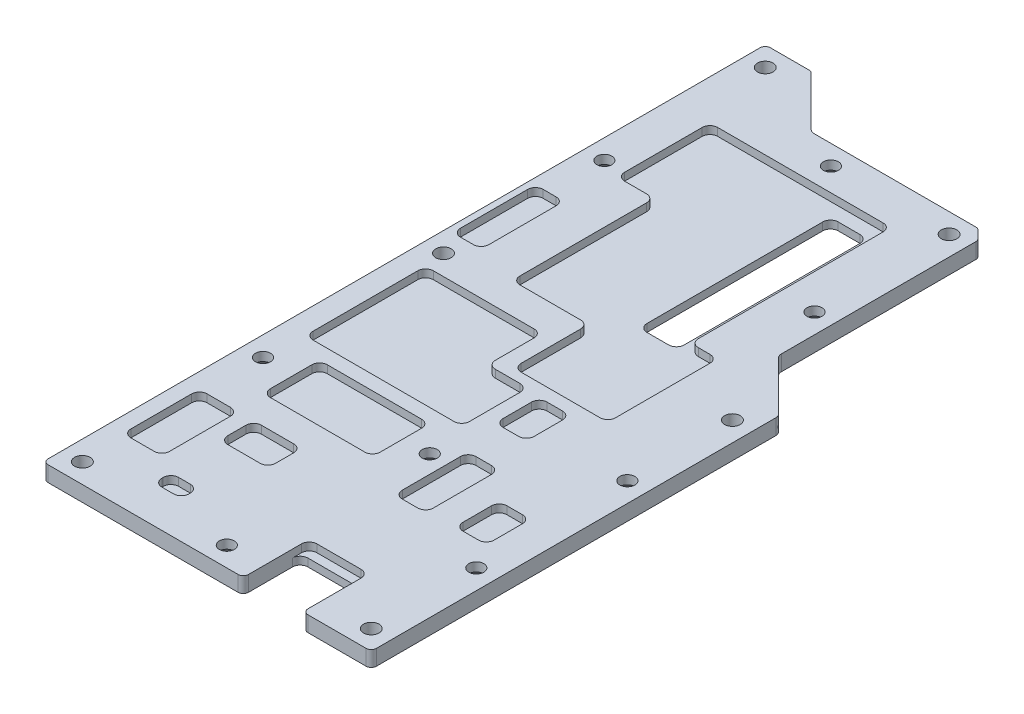
SolidWorks part; units mm, degrees
ref_plane "Front Plane" through (0, 0, 0) normal (0, 0, 1) x (1, 0, 0)
ref_plane "Top Plane" through (0, 0, 0) normal (0, 1, 0) x (1, 0, 0)
ref_plane "Right Plane" through (0, 0, 0) normal (1, 0, 0) x (0, 0, -1)
sketch "Sketch1" plane through (0, 0, 0) normal (0, 1, 0) x (1, 0, 0)
  line L0 (0, 1) -> (0, 138.7)
  line L1 (1, 0) -> (37.75, 0)
  line L2 (63.5, 1) -> (63.5, 78.3258)
  line L3 (1, 139.7) -> (8.4758, 139.7)
  line L4 (19.6713, 129.54) -> (50.8958, 129.54)
  line L5 (9.1829, 139.4071) -> (18.6107, 129.9793)
  line L6 (53.34, 89.5213) -> (53.34, 127.0958)
  line L7 (63.2071, 79.0329) -> (53.7793, 88.4607)
  line L8 (51.6029, 129.2471) -> (53.0471, 127.8029)
  line L13 (38.75, 1) -> (38.75, 9.5)
  line L14 (40.25, 11) -> (48.75, 11)
  line L15 (50.25, 9.5) -> (50.25, 1)
  line L16 (51.25, 0) -> (62.5, 0)
  arc A2 (1, 0) -> (0, 1) centre (1, 1) cw
  arc A3 (63.5, 1) -> (62.5, 0) centre (62.5, 1) cw
  arc A4 (53.7793, 88.4607) -> (53.34, 89.5213) centre (54.84, 89.5213) cw
  arc A5 (18.6107, 129.9793) -> (19.6713, 129.54) centre (19.6713, 131.04) ccw
  arc A6 (63.5, 78.3258) -> (63.2071, 79.0329) centre (62.5, 78.3258) ccw
  arc A7 (53.34, 127.0958) -> (53.0471, 127.8029) centre (52.34, 127.0958) ccw
  arc A8 (51.6029, 129.2471) -> (50.8958, 129.54) centre (50.8958, 128.54) ccw
  arc A9 (9.1829, 139.4071) -> (8.4758, 139.7) centre (8.4758, 138.7) ccw
  arc A10 (1, 139.7) -> (0, 138.7) centre (1, 138.7) ccw
  arc A13 (48.75, 11) -> (50.25, 9.5) centre (48.75, 9.5) cw
  arc A14 (38.75, 9.5) -> (40.25, 11) centre (40.25, 9.5) cw
  arc A15 (50.25, 1) -> (51.25, 0) centre (51.25, 1) ccw
  arc A16 (38.75, 1) -> (37.75, 0) centre (37.75, 1) cw
  point P20 (0, 0)
  point P23 (63.5, 0)
  point P26 (53.34, 88.9)
  point P29 (19.05, 129.54)
  point P32 (63.5, 78.74)
  point P35 (53.34, 127.51)
  point P38 (51.31, 129.54)
  point P41 (8.89, 139.7)
  point P44 (0, 139.7)
  point P45 (38.75, 11)
  point P48 (50.25, 0)
  point P51 (38.75, 0)
  dimension "D14" = 1.5
  dimension "D15" = 1
  dimension "D16" = 1
  dimension "D17" = 1.5
  dimension "D18" = 1
  dimension "D19" = 1
  dimension "D1" = 139.7
  dimension "D2" = 63.5
  dimension "D3" = 78.74
  dimension "D4" = 8.89
  dimension "D5" = 10.16
  dimension "D6" = 10.16
  dimension "D7" = 32.26
  dimension "D8" = 10.16
  dimension "D9" = 10.16
  dimension "D10" = 2.03
  dimension "D11" = 13.25
  dimension "D12" = 11.5
  dimension "D13" = 11
extrude "Boss-Extrude1" add sketch "Sketch1" along normal blind 3
sketch "Sketch2" plane through (0, 3, 0) normal (0, 1, 0) x (1, 0, 0)
  line L36 (50.25, 0) -> (50.25, 11.25)
  line L37 (51.25, 0) -> (62.5, 0) construction
  line L38 (48.75, 12.75) -> (40.25, 12.75)
  line L39 (38.75, 11.25) -> (38.75, 0)
  line L40 (1, 0) -> (37.75, 0) construction
  line L41 (38.75, 0) -> (50.25, 0)
  line L42 (63.5, 1) -> (63.5, 78.3258) construction
  line L43 (0, 138.7) -> (0, 1) construction
  line L44 (52.25, 37.5) -> (55.25, 37.5)
  line L45 (50.75, 36) -> (50.75, 30.5)
  line L46 (52.25, 29) -> (55.25, 29)
  line L47 (56.75, 36) -> (56.75, 30.5)
  line L48 (41, 42.75) -> (44, 42.75)
  line L49 (39.5, 41.25) -> (39.5, 30)
  line L50 (41, 28.5) -> (44, 28.5)
  line L51 (45.5, 41.25) -> (45.5, 30)
  line L52 (11.25, 43.75) -> (29.5, 43.75)
  line L53 (9.75, 42.25) -> (9.75, 34.25)
  line L54 (11.25, 32.75) -> (29.5, 32.75)
  line L55 (31, 42.25) -> (31, 34.25)
  line L56 (18, 10.5) -> (15.75, 10.5)
  line L57 (19.5, 9) -> (19.5, 8.75)
  line L58 (18, 7.25) -> (15.75, 7.25)
  line L59 (14.25, 9) -> (14.25, 8.75)
  line L60 (4.25, 68.25) -> (4.25, 48)
  line L61 (4.5, 27.25) -> (9, 27.25)
  line L62 (3, 25.75) -> (3, 14)
  line L63 (4.5, 12.5) -> (9, 12.5)
  line L64 (10.5, 25.75) -> (10.5, 14)
  line L65 (15, 27.25) -> (21.25, 27.25)
  line L66 (13.5, 25.75) -> (13.5, 22.25)
  line L67 (15, 20.75) -> (21.25, 20.75)
  line L68 (22.75, 25.75) -> (22.75, 22.25)
  line L69 (5.75, 46.5) -> (33, 46.5)
  line L70 (34.5, 48) -> (34.5, 57.75)
  line L71 (33, 59.25) -> (28.25, 59.25)
  line L72 (26.75, 60.75) -> (26.75, 68.25)
  line L73 (25.25, 69.75) -> (5.75, 69.75)
  line L74 (31.25, 61.25) -> (46.5, 61.25)
  line L75 (38.75, 58.75) -> (41.75, 58.75)
  line L76 (37.25, 57.25) -> (37.25, 51.75)
  line L77 (38.75, 50.25) -> (41.75, 50.25)
  line L78 (43.25, 57.25) -> (43.25, 51.75)
  line L79 (48, 62.75) -> (48, 81)
  line L80 (46.5, 82.5) -> (44.25, 82.5)
  line L81 (42.75, 84) -> (42.75, 119.75)
  line L82 (41.25, 121.25) -> (9.25, 121.25)
  line L83 (7.75, 119.75) -> (7.75, 104.75)
  line L84 (9.25, 103.25) -> (13.5, 103.25)
  line L85 (15, 101.75) -> (15, 77.25)
  line L86 (16.5, 75.75) -> (28.25, 75.75)
  line L87 (29.75, 74.25) -> (29.75, 62.75)
  line L89 (2.75, 94) -> (5.25, 94)
  line L90 (1.25, 92.5) -> (1.25, 79.5)
  line L91 (2.75, 78) -> (5.25, 78)
  line L92 (6.75, 92.5) -> (6.75, 79.5)
  arc A32 (50.25, 11.25) -> (48.75, 12.75) centre (48.75, 11.25) ccw
  arc A33 (40.25, 12.75) -> (38.75, 11.25) centre (40.25, 11.25) ccw
  arc A34 (50.75, 30.5) -> (52.25, 29) centre (52.25, 30.5) ccw
  arc A35 (55.25, 29) -> (56.75, 30.5) centre (55.25, 30.5) ccw
  arc A36 (56.75, 36) -> (55.25, 37.5) centre (55.25, 36) ccw
  arc A37 (50.75, 36) -> (52.25, 37.5) centre (52.25, 36) cw
  arc A38 (39.5, 30) -> (41, 28.5) centre (41, 30) ccw
  arc A39 (44, 28.5) -> (45.5, 30) centre (44, 30) ccw
  arc A40 (44, 42.75) -> (45.5, 41.25) centre (44, 41.25) cw
  arc A41 (41, 42.75) -> (39.5, 41.25) centre (41, 41.25) ccw
  arc A42 (29.5, 43.75) -> (31, 42.25) centre (29.5, 42.25) cw
  arc A43 (29.5, 32.75) -> (31, 34.25) centre (29.5, 34.25) ccw
  arc A44 (9.75, 34.25) -> (11.25, 32.75) centre (11.25, 34.25) ccw
  arc A45 (11.25, 43.75) -> (9.75, 42.25) centre (11.25, 42.25) ccw
  arc A46 (19.5, 8.75) -> (18, 7.25) centre (18, 8.75) cw
  arc A47 (18, 10.5) -> (19.5, 9) centre (18, 9) cw
  arc A48 (15.75, 7.25) -> (14.25, 8.75) centre (15.75, 8.75) cw
  arc A49 (15.75, 10.5) -> (14.25, 9) centre (15.75, 9) ccw
  arc A50 (21.25, 20.75) -> (22.75, 22.25) centre (21.25, 22.25) ccw
  arc A51 (21.25, 27.25) -> (22.75, 25.75) centre (21.25, 25.75) cw
  arc A52 (15, 27.25) -> (13.5, 25.75) centre (15, 25.75) ccw
  arc A53 (13.5, 22.25) -> (15, 20.75) centre (15, 22.25) ccw
  arc A54 (3, 14) -> (4.5, 12.5) centre (4.5, 14) ccw
  arc A55 (9, 12.5) -> (10.5, 14) centre (9, 14) ccw
  arc A56 (9, 27.25) -> (10.5, 25.75) centre (9, 25.75) cw
  arc A57 (4.5, 27.25) -> (3, 25.75) centre (4.5, 25.75) ccw
  arc A58 (26.75, 68.25) -> (25.25, 69.75) centre (25.25, 68.25) ccw
  arc A59 (34.5, 57.75) -> (33, 59.25) centre (33, 57.75) ccw
  arc A60 (33, 46.5) -> (34.5, 48) centre (33, 48) ccw
  arc A61 (4.25, 48) -> (5.75, 46.5) centre (5.75, 48) ccw
  arc A62 (5.75, 69.75) -> (4.25, 68.25) centre (5.75, 68.25) ccw
  arc A63 (28.25, 59.25) -> (26.75, 60.75) centre (28.25, 60.75) cw
  arc A64 (41.75, 58.75) -> (43.25, 57.25) centre (41.75, 57.25) cw
  arc A65 (41.75, 50.25) -> (43.25, 51.75) centre (41.75, 51.75) ccw
  arc A66 (37.25, 51.75) -> (38.75, 50.25) centre (38.75, 51.75) ccw
  arc A67 (38.75, 58.75) -> (37.25, 57.25) centre (38.75, 57.25) ccw
  arc A68 (42.75, 119.75) -> (41.25, 121.25) centre (41.25, 119.75) ccw
  arc A69 (44.25, 82.5) -> (42.75, 84) centre (44.25, 84) cw
  arc A70 (48, 81) -> (46.5, 82.5) centre (46.5, 81) ccw
  arc A71 (46.5, 61.25) -> (48, 62.75) centre (46.5, 62.75) ccw
  arc A72 (31.25, 61.25) -> (29.75, 62.75) centre (31.25, 62.75) cw
  arc A73 (28.25, 75.75) -> (29.75, 74.25) centre (28.25, 74.25) cw
  arc A74 (15, 77.25) -> (16.5, 75.75) centre (16.5, 77.25) ccw
  arc A75 (13.5, 103.25) -> (15, 101.75) centre (13.5, 101.75) cw
  arc A76 (7.75, 104.75) -> (9.25, 103.25) centre (9.25, 104.75) ccw
  arc A77 (9.25, 121.25) -> (7.75, 119.75) centre (9.25, 119.75) ccw
  arc A78 (1.25, 79.5) -> (2.75, 78) centre (2.75, 79.5) ccw
  arc A79 (5.25, 78) -> (6.75, 79.5) centre (5.25, 79.5) ccw
  arc A80 (5.25, 94) -> (6.75, 92.5) centre (5.25, 92.5) cw
  arc A81 (2.75, 94) -> (1.25, 92.5) centre (2.75, 92.5) ccw
  point P12 (50.25, 12.75)
  point P15 (38.75, 12.75)
  point P22 (50.75, 29)
  point P25 (56.75, 29)
  point P28 (56.75, 37.5)
  point P37 (39.5, 28.5)
  point P40 (45.5, 28.5)
  point P43 (45.5, 42.75)
  point P56 (31, 32.75)
  point P59 (9.75, 32.75)
  point P62 (9.75, 43.75)
  point P69 (19.5, 7.25)
  point P72 (19.5, 10.5)
  point P77 (14.25, 10.5)
  point P90 (22.75, 27.25)
  point P93 (13.5, 27.25)
  point P96 (13.5, 20.75)
  point P99 (3, 12.5)
  point P104 (10.5, 27.25)
  point P107 (3, 27.25)
  point P117 (26.75, 69.75)
  point P120 (34.5, 59.25)
  point P123 (34.5, 46.5)
  point P126 (4.25, 46.5)
  point P129 (4.25, 69.75)
  point P137 (43.25, 58.75)
  point P142 (37.25, 50.25)
  point P145 (37.25, 58.75)
  point P158 (42.75, 121.25)
  point P161 (42.75, 82.5)
  point P164 (48, 82.5)
  point P167 (48, 61.25)
  point P170 (29.75, 61.25)
  point P175 (15, 75.75)
  point P178 (15, 103.25)
  point P181 (7.75, 103.25)
  point P184 (7.75, 121.25)
  point P192 (1.25, 78)
  point P197 (6.75, 94)
  point P200 (1.25, 94)
  dimension "D35" = 30.25
  dimension "D36" = 12.75
  dimension "D37" = 22.5
  dimension "D38" = 4.25
  dimension "D39" = 46.5
  dimension "D40" = 1.5
  dimension "D41" = 1.5
  dimension "D42" = 8.5
  dimension "D4" = 1.5
  dimension "D9" = 1.5
  dimension "D14" = 1.5
  dimension "D19" = 1.5
  dimension "D24" = 1.5
  dimension "D33" = 1.5
  dimension "D46" = 1.5
  dimension "D57" = 1.5
  dimension "D62" = 1.5
  dimension "D1" = 13.25
  dimension "D2" = 12.75
  dimension "D3" = 11.5
  dimension "D5" = 6
  dimension "D6" = 8.5
  dimension "D7" = 6.75
  dimension "D8" = 29
  dimension "D10" = 14.25
  dimension "D11" = 6
  dimension "D12" = 18
  dimension "D13" = 28.5
  dimension "D15" = 21.25
  dimension "D16" = 11
  dimension "D17" = 32.75
  dimension "D18" = 9.75
  dimension "D20" = 3.25
  dimension "D21" = 5.25
  dimension "D22" = 7.25
  dimension "D23" = 14.25
  dimension "D25" = 14.75
  dimension "D26" = 7.5
  dimension "D27" = 12.5
  dimension "D28" = 3
  dimension "D29" = 6.5
  dimension "D30" = 9.25
  dimension "D31" = 13.5
  dimension "D32" = 20.75
  dimension "D34" = 23.25
  dimension "D43" = 6
  dimension "D44" = 20.25
  dimension "D45" = 50.25
  dimension "D47" = 18.25
  dimension "D48" = 21.25
  dimension "D49" = 5.25
  dimension "D50" = 38.75
  dimension "D51" = 35
  dimension "D52" = 18
  dimension "D53" = 7.25
  dimension "D54" = 27.5
  dimension "D55" = 15.5
  dimension "D56" = 61.25
  dimension "D58" = 16
  dimension "D59" = 5.5
  dimension "D60" = 1.25
  dimension "D61" = 78
extrude "Cut-Extrude1" cut sketch "Sketch2" against normal blind 1.5
sketch "Sketch3" plane through (0, 0, 0) normal (0, -1, 0) x (-1, 0, 0)
  line L0 (-37.34, 118.58) -> (-37.34, 81.58) construction
  line L1 (-39.44, 118.58) -> (-35.24, 118.58)
  line L2 (-40.94, 117.08) -> (-40.94, 83.08)
  line L3 (-39.44, 81.58) -> (-35.24, 81.58)
  line L4 (-33.74, 117.08) -> (-33.74, 83.08)
  line L5 (-40.94, 100.08) -> (-33.74, 100.08) construction
  arc A0 (-40.94, 83.08) -> (-39.44, 81.58) centre (-39.44, 83.08) ccw
  arc A1 (-35.24, 81.58) -> (-33.74, 83.08) centre (-35.24, 83.08) ccw
  arc A2 (-35.24, 118.58) -> (-33.74, 117.08) centre (-35.24, 117.08) cw
  arc A3 (-39.44, 118.58) -> (-40.94, 117.08) centre (-39.44, 117.08) ccw
  point P12 (-40.94, 81.58)
  point P17 (-33.74, 118.58)
  point P20 (-40.94, 118.58)
  dimension "D5" = 1.5
  dimension "D1" = 37
  dimension "D2" = 7.2
  dimension "D3" = 37.34
  dimension "D4" = 100.08
extrude "Cut-Extrude2" cut sketch "Sketch3" against normal up to next
hole_wizard "Ø3.0mm Dowel Hole1" positions "Sketch5" profile "Sketch6" hole size "Ø3.0" standard "ISO" end condition through all
sketch "Sketch5" plane through (0, 3, 0) normal (0, 1, 0) x (1, 0, 0)
  line L0 (51.25, 0) -> (62.5, 0) construction
  line L1 (63.5, 1) -> (63.5, 78.3258) construction
  line L2 (53.34, 89.5213) -> (53.34, 127.0958) construction
  line L3 (50.8958, 129.54) -> (19.6713, 129.54) construction
  line L4 (0, 138.7) -> (0, 1) construction
  line L5 (8.4758, 139.7) -> (1, 139.7) construction
  line L6 (1, 0) -> (37.75, 0) construction
  point P0 (3.81, 135.89)
  point P2 (49.53, 125.73)
  point P4 (59.69, 73.66)
  point P6 (59.69, 3.81)
  point P8 (3.81, 3.81)
  point P10 (3.81, 73.66)
  dimension "D1" = 3.81
  dimension "D2" = 3.81
  dimension "D3" = 3.81
  dimension "D4" = 3.81
  dimension "D5" = 3.81
  dimension "D6" = 3.81
  dimension "D7" = 3.81
  dimension "D8" = 3.81
  dimension "D9" = 3.81
  dimension "D10" = 3.81
  dimension "D11" = 69.85
  dimension "D12" = 69.85
sketch "Sketch6" plane through (3.81, 3, -135.89) normal (1, 0, 0) x (0, 0, 1)
  line L0 (0, 0) -> (0, 3)
  line L1 (0, 3) -> (1.5, 3)
  line L2 (1.5, 3) -> (1.5, 0)
  line L5 (1.5, 0) -> (0, 0)
  line L11 (0, -6.35) -> (0, 107.95) construction
  dimension "Thru Hole Dia." = 3
  dimension "Thru Hole Depth" = 3
hole_wizard "CSK for M2.5 Countersunk Raised Head Screw1" positions "Sketch7" profile "Sketch8" countersink size "M2.5" standard "ISO" end condition through all
sketch "Sketch7" plane through (0, 0, 0) normal (0, -1, 0) x (-1, 0, 0)
  line L0 (0, 138.7) -> (0, 1) construction
  line L1 (-50.8958, 129.54) -> (-19.6713, 129.54) construction
  line L2 (-1, 0) -> (-37.75, 0) construction
  line L3 (-63.5, 1) -> (-63.5, 78.3258) construction
  line L4 (-53.34, 89.5213) -> (-53.34, 127.0958) construction
  circle A0 centre (-59.69, 3.81) radius 1.5 construction
  circle A2 centre (-3.81, 3.81) radius 1.5 construction
  circle A3 centre (-3.81, 135.89) radius 1.5 construction
  circle A4 centre (-49.53, 125.73) radius 1.5 construction
  point P0 (-26.67, 125.73)
  point P2 (-31.75, 3.81)
  point P4 (-59.69, 53.34)
  point P6 (-3.81, 38.74)
  point P8 (-36.07, 38.74)
  point P10 (-59.69, 24.13)
  point P12 (-49.53, 99.69)
  point P14 (-3.81, 104.77)
  dimension "D1" = 3.81
  dimension "D2" = 3.81
  dimension "D3" = 3.81
  dimension "D4" = 3.81
  dimension "D5" = 3.81
  dimension "D6" = 3.81
  dimension "D7" = 3.81
  dimension "D8" = 49.53
  dimension "D9" = 20.32
  dimension "D10" = 32.26
  dimension "D11" = 27.94
  dimension "D12" = 34.93
  dimension "D13" = 31.12
  dimension "D14" = 26.04
  dimension "D15" = 22.86
sketch "Sketch8" plane through (26.67, 0, -125.73) normal (1, 0, 0) x (0, 0, -1)
  line L0 (0, 0) -> (0, 3)
  line L1 (0, 3) -> (1.45, 3)
  line L2 (1.45, 3) -> (1.45, 1.3)
  line L3 (1.45, 1.3) -> (2.75, 0)
  line L5 (2.75, 0) -> (0, 0)
  line L6 (-1.45, 1.3) -> (-2.75, 0) construction
  line L11 (0, -6.35) -> (0, 107.95) construction
  dimension "Thru Hole Dia." = 2.9
  dimension "Thru Hole Depth" = 3
  dimension "Near C'Sink Dia." = 5.5
  dimension "Near C'Sink Angle" = 90
